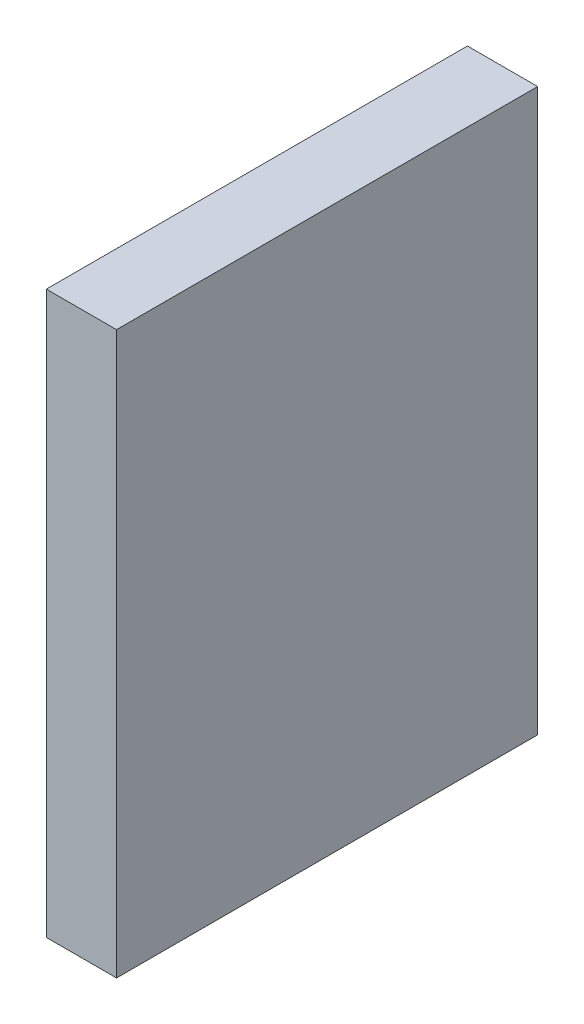
SolidWorks part; units mm, degrees
ref_plane "Front Plane" through (0, 0, 0) normal (0, 0, 1) x (1, 0, 0)
ref_plane "Top Plane" through (0, 0, 0) normal (0, 1, 0) x (1, 0, 0)
ref_plane "Right Plane" through (0, 0, 0) normal (1, 0, 0) x (0, 0, -1)
sketch "Sketch1" plane through (0, 0, 0) normal (0, 0, 1) x (1, 0, 0)
  line L1 (0, 0) -> (6.35, 0)
  line L2 (0, 0) -> (0, 50.8)
  line L3 (0, 50.8) -> (6.35, 50.8)
  line L4 (6.35, 0) -> (6.35, 50.8)
extrude "Boss-Extrude1" add sketch "Sketch1" along normal blind 38.1
sketch "Sketch2" plane through (6.35, 0, 0) normal (1, 0, 0) x (0, 0, -1)
  line L0 (0, 0) -> (0, 50.8) construction
  line L1 (-38.1, 0) -> (0, 0)
  line L2 (-38.1, 0) -> (-38.1, 6.35)
  line L3 (-38.1, 6.35) -> (0, 6.35)
  line L4 (0, 0) -> (0, 6.35)
  line L5 (-38.1, 3.175) -> (-31.75, 3.175)
  line L6 (0, 3.175) -> (-6.35, 3.175)
  line L7 (-31.75, 3.175) -> (-6.35, 3.175)
  circle A0 centre (-31.75, 3.175) radius 1.25
  dimension "D3" = 2.5
  dimension "D1" = 6.35
  dimension "D2" = 6.35
